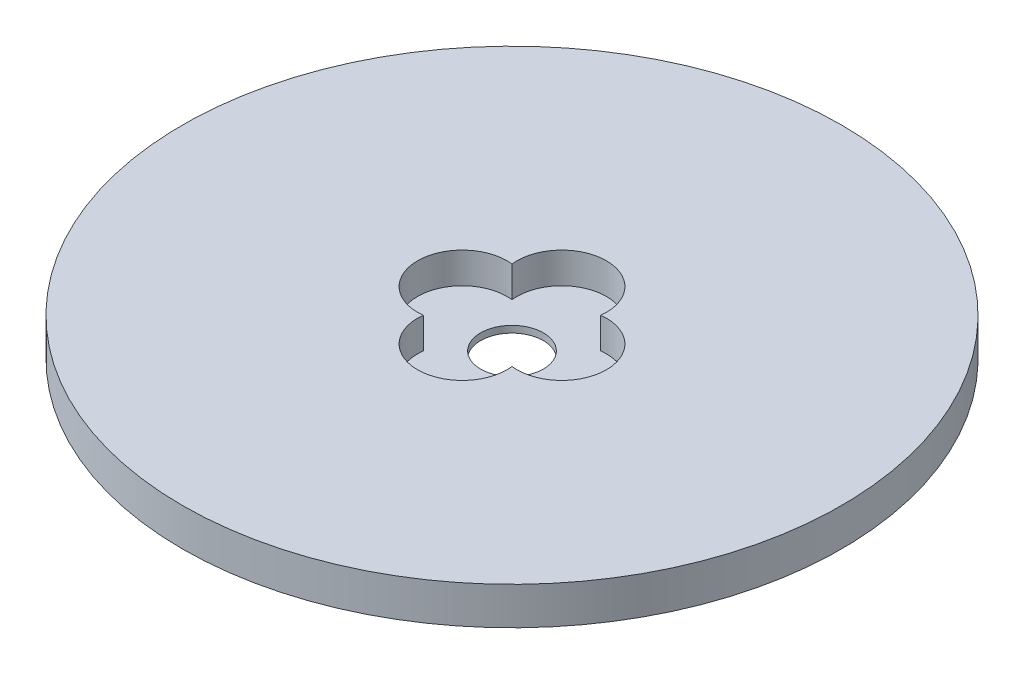
SolidWorks part; units mm, degrees
ref_plane "Front Plane" through (0, 0, 0) normal (0, 0, 1) x (1, 0, 0)
ref_plane "Top Plane" through (0, 0, 0) normal (0, 1, 0) x (1, 0, 0)
ref_plane "Right Plane" through (0, 0, 0) normal (1, 0, 0) x (0, 0, -1)
sketch "Sketch1" plane through (0, 0, 0) normal (0, 1, 0) x (1, 0, 0)
  circle A0 centre (0, 0) radius 52.5
  dimension "FLANGE_OD" = 105
extrude "Boss-Extrude1" add sketch "Sketch1" along normal blind 6
sketch "Sketch2" plane through (0, 0, 0) normal (0, 1, 0) x (1, 0, 0)
  circle A0 centre (0, 0) radius 5
  dimension "BORE_D" = 10
extrude "Cut-Extrude1" cut sketch "Sketch2" along normal through all
sketch "Sketch3" plane through (0, 6, 0) normal (0, 1, 0) x (1, 0, 0)
  circle A0 centre (0, 0) radius 7.922 construction
  circle A1 centre (-7.922, 0) radius 7.1204
  dimension "BOLT_D" = 14.2408
  dimension "BOLT_PCD" = 15.844
extrude "Cut-Extrude2" cut sketch "Sketch3" against normal blind 4.924
pattern_circular "CirPattern1" count 4 over 360 about axis through (0, 0, 0) along (0, 1, 0) of "Cut-Extrude2"
